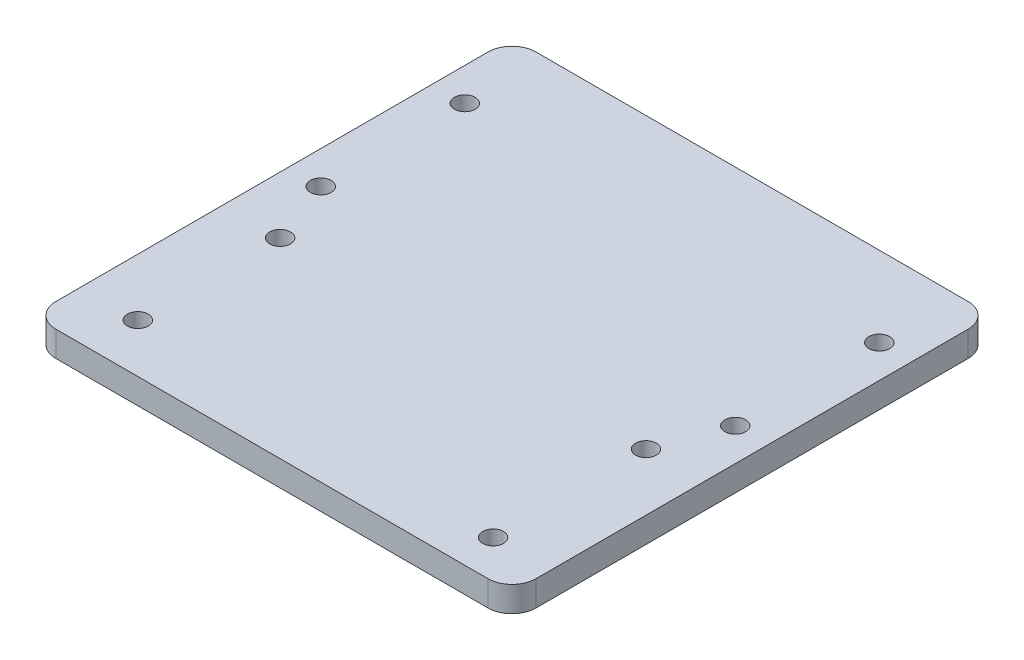
SolidWorks part; units mm, degrees
ref_plane "Front Plane" through (0, 0, 0) normal (0, 0, 1) x (1, 0, 0)
ref_plane "Top Plane" through (0, 0, 0) normal (0, 1, 0) x (1, 0, 0)
ref_plane "Right Plane" through (0, 0, 0) normal (1, 0, 0) x (0, 0, -1)
sketch "Sketch1" plane through (0, 0, 0) normal (0, 1, 0) x (1, 0, 0)
  line L1 (-30, 30) -> (30, 30)
  line L2 (-30, 30) -> (-30, -30)
  line L3 (-30, -30) -> (30, -30)
  line L4 (30, 30) -> (30, -30)
  line L5 (-30, 30) -> (30, -30) construction
  line L6 (-30, -30) -> (30, 30) construction
  point P0 (0, 0)
  dimension "D1" = 60
  dimension "D2" = 60
extrude "Boss-Extrude1" add sketch "Sketch1" along normal blind 3.175
sketch "Sketch2" plane through (0, 3.175, 0) normal (0, 1, 0) x (1, 0, 0)
  line L0 (0, 30) -> (0, -30) construction
  line L1 (30, 30) -> (-30, 30) construction
  line L2 (-30, -30) -> (30, -30) construction
  line L3 (-30, 30) -> (-30, -30) construction
  circle A0 centre (-25.9, 20) radius 1.3
  circle A1 centre (-25.9, 2) radius 1.3
  circle A2 centre (25.9, 2) radius 1.3
  circle A3 centre (25.9, 20) radius 1.3
  point P11 (-24.6, 20)
  point P17 (24.6, 20)
  dimension "D1" = 2.6
  dimension "D2" = 18
  dimension "D3" = 5.4
  dimension "D4" = 10
extrude "Cut-Extrude1" cut sketch "Sketch2" against normal up to surface (3.175 mm away) up to face at (0, 0, 0)
fillet "Fillet1" radius 3 4 edges at (-30, 1.5875, 30) (30, 1.5875, 30) (30, 1.5875, -30) (-30, 1.5875, -30)
sketch "Sketch3" plane through (0, 3.175, 0) normal (0, 1, 0) x (1, 0, 0)
  line L0 (-30, 0) -> (30, 0) construction
  line L1 (-22.865, -6.11) -> (22.855, -6.11) construction
  line L2 (-22.865, -6.11) -> (-22.865, -23.89) construction
  line L3 (-22.865, -23.89) -> (22.855, -25.22) construction
  line L4 (22.855, -6.11) -> (22.855, -25.22) construction
  line L5 (-30, 27) -> (-30, -27) construction
  line L6 (30, -27) -> (30, 27) construction
  circle A0 centre (-22.865, -6.11) radius 1.3
  circle A1 centre (22.855, -6.11) radius 1.3
  circle A2 centre (22.855, -25.22) radius 1.3
  circle A3 centre (-22.865, -23.89) radius 1.3
  dimension "D1" = 2.6
  dimension "D2" = 45.72
  dimension "D3" = 17.78
  dimension "D4" = 19.11
extrude "Cut-Extrude2" cut sketch "Sketch3" against normal up to surface (3.175 mm away) up to face at (25.9, 0, -18.7)
